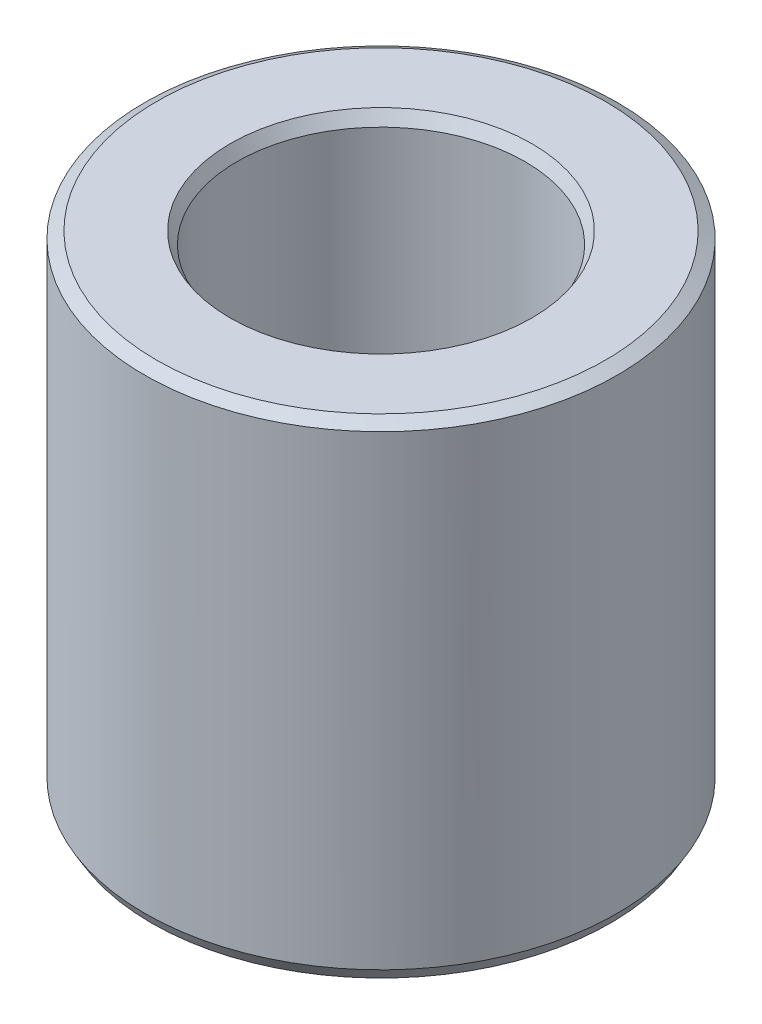
SolidWorks part; units mm, degrees
ref_plane "Front Plane" through (0, 0, 0) normal (0, 0, 1) x (1, 0, 0)
ref_plane "Top Plane" through (0, 0, 0) normal (0, 1, 0) x (1, 0, 0)
ref_plane "Right Plane" through (0, 0, 0) normal (1, 0, 0) x (0, 0, -1)
sketch "Sketch1" plane through (0, 0, 0) normal (0, 1, 0) x (1, 0, 0)
  circle A0 centre (0, 0) radius 10
  dimension "SLEEVE_OD" = 20
extrude "Boss-Extrude1" add sketch "Sketch1" along normal blind 20.5286
sketch "Sketch2" plane through (0, 0, 0) normal (0, 1, 0) x (1, 0, 0)
  circle A0 centre (0, 0) radius 6.0947
  dimension "BORE_D" = 12.1895
extrude "Cut-Extrude1" cut sketch "Sketch2" along normal through all
chamfer "Chamfer1" distance 0.2937 angle 60 4 edges at (0, 20.5286, 6.0947) (0, 0, 6.0947) (0, 0, 10) (0, 20.5286, 10) first distance on face at (0, 20.5286, 6.0947) first distance on face at (0, 0, 6.0947) first distance on face at (0, 20.5286, 10)
